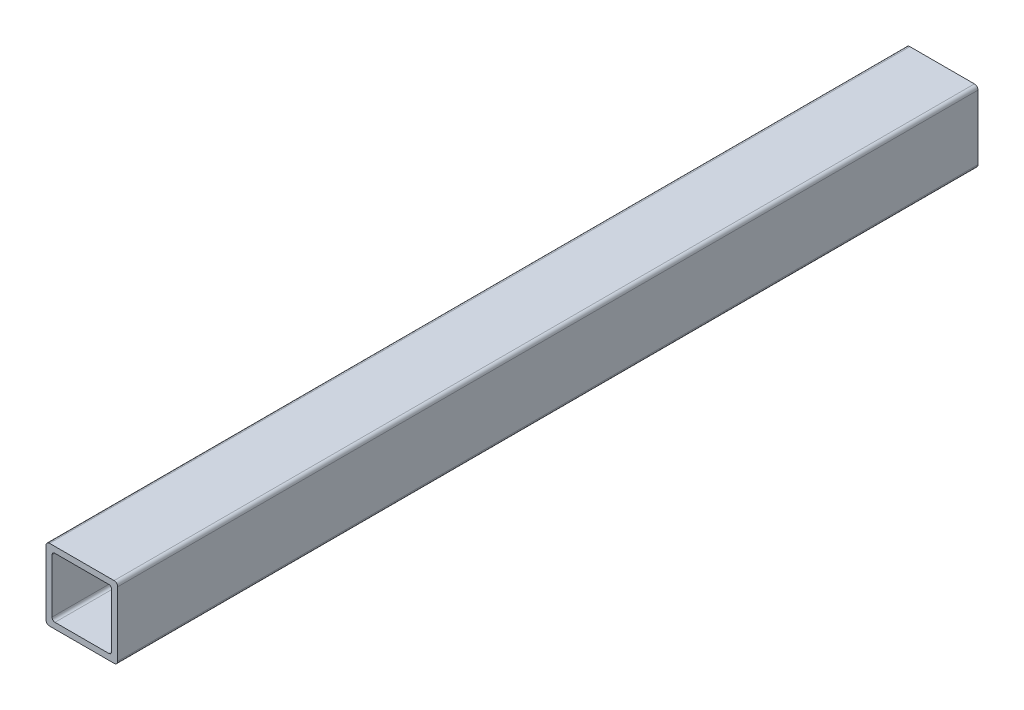
SolidWorks part; units mm, degrees
ref_plane "Front" through (0, 0, 0) normal (0, 0, 1) x (1, 0, 0)
ref_plane "Top" through (0, 0, 0) normal (0, 1, 0) x (1, 0, 0)
ref_plane "Right" through (0, 0, 0) normal (1, 0, 0) x (0, 0, -1)
sketch "Sketch1" plane through (0, 0, 0) normal (0, 0, 1) x (1, 0, 0)
  line L0 (-31.75, 0) -> (-38.1, 0) construction
  line L1 (34.29, -38.1) -> (-34.29, -38.1)
  line L2 (38.1, -34.29) -> (38.1, 34.29)
  line L3 (34.29, 38.1) -> (-34.29, 38.1)
  line L4 (-38.1, -34.29) -> (-38.1, 34.29)
  line L5 (38.1, -38.1) -> (-38.1, 38.1) construction
  line L6 (38.1, 38.1) -> (-38.1, -38.1) construction
  line L7 (28.575, 31.75) -> (-28.575, 31.75)
  line L8 (31.75, 28.575) -> (31.75, -28.575)
  line L9 (28.575, -31.75) -> (-28.575, -31.75)
  line L10 (-31.75, 28.575) -> (-31.75, -28.575)
  line L11 (31.75, 31.75) -> (-31.75, -31.75) construction
  line L12 (31.75, -31.75) -> (-31.75, 31.75) construction
  line L13 (0, -31.75) -> (0, -38.1) construction
  line L14 (31.75, -28.575) -> (31.75, -38.1) construction
  line L16 (31.75, -38.1) -> (38.1, -38.1) construction
  arc A0 (-28.575, -31.75) -> (-31.75, -28.575) centre (-28.575, -28.575) cw
  arc A1 (31.75, -28.575) -> (28.575, -31.75) centre (28.575, -28.575) cw
  arc A2 (28.575, 31.75) -> (31.75, 28.575) centre (28.575, 28.575) cw
  arc A3 (-28.575, 31.75) -> (-31.75, 28.575) centre (-28.575, 28.575) ccw
  arc A4 (34.29, -38.1) -> (38.1, -34.29) centre (34.29, -34.29) ccw
  arc A5 (38.1, 34.29) -> (34.29, 38.1) centre (34.29, 34.29) ccw
  arc A6 (-34.29, 38.1) -> (-38.1, 34.29) centre (-34.29, 34.29) ccw
  arc A7 (-34.29, -38.1) -> (-38.1, -34.29) centre (-34.29, -34.29) cw
  point P0 (0, 0)
  point P6 (0, 0)
  dimension "D2" = 3.175
  dimension "D3" = 3.81
sketch "Sketch2" plane through (0, 0, 0) normal (1, 0, 0) x (0, 0, -1)
  line L0 (-457.2, 0) -> (457.2, 0) construction
  dimension "Length" = 914.4
ref_plane "Plane1" through (38.1, 0, 0) normal (1, 0, 0) x (0, 0, -1)
sketch "Sketch5" plane through (38.1, 0, 0) normal (1, 0, 0) x (0, 0, -1)
  line L0 (-457.2, 38.1) -> (-457.2, -38.1) construction
  line L1 (457.2, 38.1) -> (457.2, -38.1) construction
sketch "Sketch4" plane through (0, 0, 0) normal (0, 0, 1) x (1, 0, 0)
  line L0 (38.1, -34.29) -> (38.1, 34.29) construction
  line L1 (34.29, 38.1) -> (-34.29, 38.1) construction
  line L2 (-38.1, -34.29) -> (-38.1, 34.29) construction
  line L3 (34.29, -38.1) -> (-34.29, -38.1) construction
  line L4 (31.75, 28.575) -> (31.75, -28.575) construction
  line L5 (28.575, -31.75) -> (-28.575, -31.75) construction
  line L6 (-31.75, 28.575) -> (-31.75, -28.575) construction
  line L7 (28.575, 31.75) -> (-28.575, 31.75) construction
  line L8 (38.1, -34.29) -> (38.1, 34.29)
  line L9 (34.29, 38.1) -> (-34.29, 38.1)
  line L10 (-38.1, -34.29) -> (-38.1, 34.29)
  line L11 (34.29, -38.1) -> (-34.29, -38.1)
  line L12 (31.75, 28.575) -> (31.75, -28.575)
  line L13 (28.575, -31.75) -> (-28.575, -31.75)
  line L14 (-31.75, 28.575) -> (-31.75, -28.575)
  line L15 (28.575, 31.75) -> (-28.575, 31.75)
  arc A0 (38.1, 34.29) -> (34.29, 38.1) centre (34.29, 34.29) ccw construction
  arc A1 (-34.29, 38.1) -> (-38.1, 34.29) centre (-34.29, 34.29) ccw construction
  arc A2 (-38.1, -34.29) -> (-34.29, -38.1) centre (-34.29, -34.29) ccw construction
  arc A3 (34.29, -38.1) -> (38.1, -34.29) centre (34.29, -34.29) ccw construction
  arc A4 (28.575, -31.75) -> (31.75, -28.575) centre (28.575, -28.575) ccw construction
  arc A5 (-31.75, -28.575) -> (-28.575, -31.75) centre (-28.575, -28.575) ccw construction
  arc A6 (-28.575, 31.75) -> (-31.75, 28.575) centre (-28.575, 28.575) ccw construction
  arc A7 (31.75, 28.575) -> (28.575, 31.75) centre (28.575, 28.575) ccw construction
  arc A8 (38.1, 34.29) -> (34.29, 38.1) centre (34.29, 34.29) ccw
  arc A9 (-34.29, 38.1) -> (-38.1, 34.29) centre (-34.29, 34.29) ccw
  arc A10 (-38.1, -34.29) -> (-34.29, -38.1) centre (-34.29, -34.29) ccw
  arc A11 (34.29, -38.1) -> (38.1, -34.29) centre (34.29, -34.29) ccw
  arc A12 (28.575, -31.75) -> (31.75, -28.575) centre (28.575, -28.575) ccw
  arc A13 (-31.75, -28.575) -> (-28.575, -31.75) centre (-28.575, -28.575) ccw
  arc A14 (-28.575, 31.75) -> (-31.75, 28.575) centre (-28.575, 28.575) ccw
  arc A15 (31.75, 28.575) -> (28.575, 31.75) centre (28.575, 28.575) ccw
extrude "Boss-Extrude1" add sketch "Sketch4" along normal up to vertex (457.2 mm away) and the other way up to vertex (457.2 mm away) up to point (0, 0, 457.2) other way up to point (0, 0, -457.2)
equation "\"D3@Sketch1\"=\"Outside Width@Sketch1\"*.05"
equation "\"D2@Sketch1\"=\"D1@Sketch1\"*.05"
